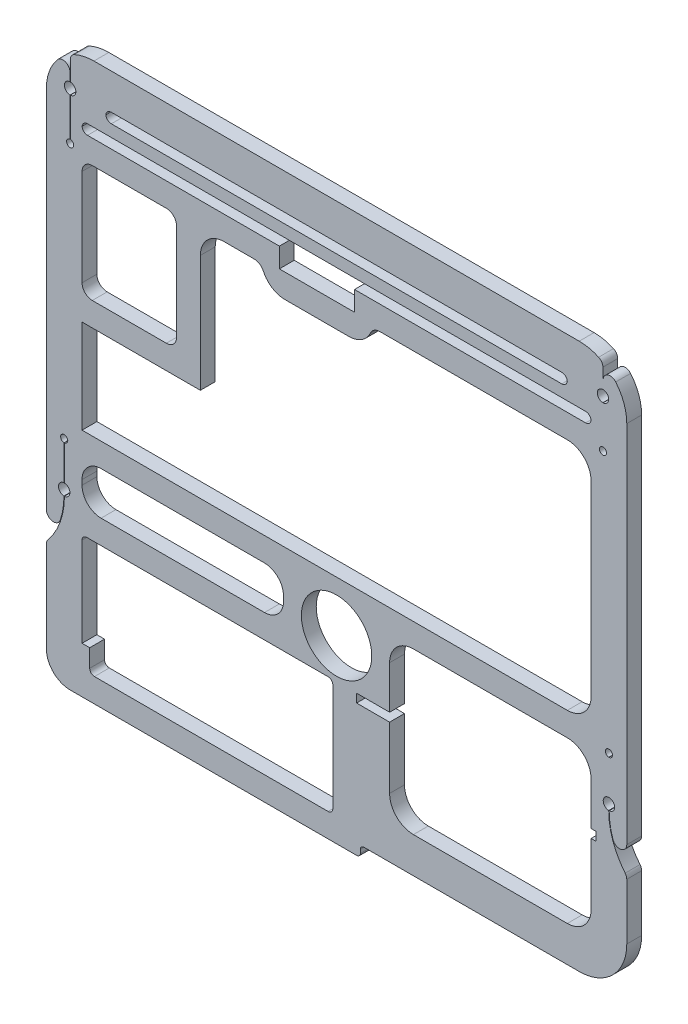
SolidWorks part; units mm, degrees
ref_plane "Front Plane" through (0, 0, 0) normal (0, 0, 1) x (1, 0, 0)
ref_plane "Top Plane" through (0, 0, 0) normal (0, 1, 0) x (1, 0, 0)
ref_plane "Right Plane" through (0, 0, 0) normal (1, 0, 0) x (0, 0, -1)
sketch "Sketch1" plane through (0, 0, 0) normal (0, 0, 1) x (1, 0, 0)
  line L0 (63.9883, 50.6392) -> (63.9883, 46.8292) construction
  line L1 (4.1102, -7.651) -> (66.0868, -7.651)
  line L2 (4.1102, -7.651) -> (4.1102, 50.6392)
  line L3 (4.1102, 50.6392) -> (66.0868, 50.6392)
  line L4 (66.0868, -7.651) -> (66.0868, 50.6392)
  line L5 (62.2768, 46.8292) -> (7.9202, 46.8292)
  line L6 (62.2768, 46.8292) -> (62.2768, -3.841)
  line L7 (62.2768, -3.841) -> (7.9202, -3.841)
  line L8 (7.9202, 46.8292) -> (7.9202, -3.841)
  line L9 (63.9883, 48.7342) -> (18.0707, 48.7342) construction
  line L10 (7.9202, 41.2855) -> (4.1102, 41.2855) construction
  line L11 (6.0152, 41.2855) -> (6.0152, 25.8577) construction
  line L12 (13.5248, -3.841) -> (13.5248, -7.651) construction
  line L13 (13.5248, -5.746) -> (21.1598, -5.746) construction
  line L14 (66.0868, 38.1916) -> (62.2768, 38.1916) construction
  line L15 (64.1818, 38.1916) -> (64.1818, 22.3321) construction
  line L16 (62.2768, 17.3639) -> (62.2768, 41.7492) construction
  line L17 (7.9202, 36.7962) -> (7.9202, 17.3639) construction
  line L22 (34.9556, 48.7342) -> (35.5018, 48.7342) construction
  line L23 (52.4244, -5.746) -> (51.8782, -5.746) construction
  dimension "D1" = 3.81
  dimension "D2" = 3.81
extrude "Boss-Extrude1" add sketch "Sketch1" along normal blind 1.5875
sketch "Sketch2" plane through (0, 0, 0) normal (0, 0, -1) x (-1, 0, 0)
  line L0 (-62.2768, -3.841) -> (-62.2768, 46.8292) construction
  line L1 (-62.2768, 15.868) -> (-7.9202, 15.868)
  line L2 (-62.2768, 15.868) -> (-62.2768, 13.328)
  line L3 (-62.2768, 13.328) -> (-7.9202, 13.328)
  line L4 (-7.9202, 15.868) -> (-7.9202, 13.328)
  line L5 (-7.9202, 46.8292) -> (-7.9202, -3.841) construction
  line L6 (-13.0532, 15.868) -> (-50.7532, 15.868) construction
  line L8 (-55.2788, 43.4256) -> (-16.9248, 43.4256) construction
  line L9 (-36.3812, 41.3174) -> (-29.6248, 41.3174) construction
  line L10 (-36.3812, 43.4256) -> (-36.3812, 41.3174) construction
  line L11 (-62.2768, 43.4256) -> (-37.0162, 43.4256)
  line L12 (-62.2768, 43.4256) -> (-62.2768, 40.8856)
  line L13 (-62.2768, 40.8856) -> (-38.9212, 40.8856)
  line L14 (-7.9202, 43.4256) -> (-7.9202, 40.8856)
  line L15 (-62.2768, 45.7624) -> (-7.9202, 45.7624)
  line L16 (-62.2768, 45.7624) -> (-62.2768, 44.4924)
  line L17 (-62.2768, 44.4924) -> (-7.9202, 44.4924)
  line L18 (-7.9202, 45.7624) -> (-7.9202, 44.4924)
  line L19 (-29.6248, 41.3174) -> (-29.6248, 43.4256) construction
  line L20 (-36.3812, 43.4256) -> (-36.3812, 41.3174) construction
  line L21 (-29.6248, 41.3174) -> (-29.6248, 43.4256) construction
  line L22 (-37.0162, 41.3174) -> (-37.0162, 43.4256)
  line L23 (-28.9898, 41.3174) -> (-37.0162, 41.3174)
  line L24 (-28.9898, 41.3174) -> (-28.9898, 43.4256)
  line L25 (-38.9212, 40.8856) -> (-38.9212, 38.7774)
  line L26 (-38.9212, 38.7774) -> (-27.0848, 38.7774)
  line L27 (-27.0848, 38.7774) -> (-27.0848, 40.8856)
  line L28 (-27.0848, 40.8856) -> (-7.9202, 40.8856)
  line L29 (-28.9898, 43.4256) -> (-7.9202, 43.4256)
  line L30 (-37.0162, 42.249) -> (-36.3812, 42.249) construction
  line L31 (-57.9086, 46.8292) -> (-57.9086, 45.7624) construction
  line L32 (-29.6248, 42.1673) -> (-28.9898, 42.1673) construction
  line L33 (-62.2768, 46.8292) -> (-7.9202, 46.8292) construction
  line L35 (-57.9086, 44.4924) -> (-57.9086, 43.4256) construction
  dimension "D1" = 2.54
  dimension "D2" = 1.905
  dimension "D3" = 2.54
  dimension "D4" = 1.905
  dimension "D5" = 1.27
  dimension "D6" = 0.635
extrude "Boss-Extrude2" add sketch "Sketch2" against normal up to surface (1.5875 mm away) up to face at (35.0985, 21.4941, 1.5875)
sketch "Sketch3" plane through (0, 0, 0) normal (0, 0, -1) x (-1, 0, 0)
  line L1 (-16.3032, 25.868) -> (-7.9202, 25.868) construction
  line L12 (-20.5532, 25.868) -> (-13.0532, 25.868)
  line L13 (-13.0532, 25.868) -> (-7.9202, 25.868)
  line L14 (-7.9202, 40.8856) -> (-7.9202, 15.868) construction
  line L15 (-7.9202, 25.868) -> (-7.9202, 28.408)
  line L16 (-7.9202, 28.408) -> (-18.0132, 28.408)
  line L17 (-18.0132, 28.408) -> (-18.0132, 40.8856)
  line L18 (-27.0848, 40.8856) -> (-7.9202, 40.8856) construction
  line L19 (-18.0132, 40.8856) -> (-20.5532, 40.8856)
  line L20 (-20.5532, 40.8856) -> (-20.5532, 25.868)
  line M27 (-27.0848, 40.8856) -> (-7.9202, 40.8856)
  line M28 (-7.9202, 40.8856) -> (-7.9202, 15.868)
  dimension "D3" = 2.54
  dimension "D4" = 2.54
extrude "Boss-Extrude3" add sketch "Sketch3" against normal up to surface (1.5875 mm away) contours L20 L12 L13 L16 L17 M27 M28 region at (20.3569, 33.3768, 0) up to face at (35.0985, 46.2958, 1.5875)
sketch "Sketch4" plane through (0, 0, 0) normal (0, 0, -1) x (-1, 0, 0)
  line L0 (-62.2768, 13.328) -> (-7.9202, 13.328) construction
  line L1 (-40.7627, 13.328) -> (-29.4343, 13.328)
  line L2 (-40.7627, 13.328) -> (-40.7627, -3.841)
  line L3 (-40.7627, -3.841) -> (-29.4343, -3.841)
  line L4 (-29.4343, 13.328) -> (-29.4343, -3.841)
  line L5 (-7.9202, -3.841) -> (-62.2768, -3.841) construction
  line L6 (-38.8577, 10.4578) -> (-40.7627, 10.4578) construction
  line L7 (-31.3393, 10.4578) -> (-29.4343, 10.4578) construction
  dimension "D1" = 1.905
extrude "Boss-Extrude4" add sketch "Sketch4" against normal up to surface (1.5875 mm away) up to face at (12.9667, 34.6468, 1.5875)
sketch "Sketch5" plane through (0, 0, 0) normal (0, 0, -1) x (-1, 0, 0)
  line L1 (-8.7364, -6.254) -> (-34.6952, -6.254) construction
  line L2 (-8.7364, -6.254) -> (-8.7364, 6.2047) construction
  line L6 (-8.7364, 6.2047) -> (-34.6952, 6.2047) construction
  line L7 (-34.6952, -6.254) -> (-34.6952, 6.2047) construction
  line L8 (-8.7364, -6.254) -> (-34.6952, -6.254)
  line L9 (-8.7364, -6.254) -> (-8.7364, 6.2047)
  line L10 (-8.7364, 6.2047) -> (-34.6952, 6.2047)
  line L11 (-34.6952, -6.254) -> (-34.6952, 6.2047)
  circle A1 centre (-35.0985, 10.4578) radius 3.7592 construction
  circle A2 centre (-35.0985, 10.4578) radius 3.7592
extrude "Cut-Extrude1" cut sketch "Sketch5" against normal up to surface (1.5875 mm away) up to face at (51.5197, 4.7435, 1.5875)
sketch "Sketch10" plane through (0, 0, 1.5875) normal (0, 0, 1) x (1, 0, 0)
  line L0 (29.4343, 13.328) -> (29.4343, 6.2047) construction
  line L1 (7.9202, 6.2047) -> (29.4343, 6.2047)
  line L2 (7.9202, 6.2047) -> (7.9202, 8.7447)
  line L3 (7.9202, 8.7447) -> (29.4343, 8.7447)
  line L4 (29.4343, 6.2047) -> (29.4343, 8.7447)
  line L5 (7.9202, 13.328) -> (7.9202, -3.841) construction
  line L6 (34.6952, 6.2047) -> (29.4343, 6.2047) construction
  dimension "D1" = 2.54
extrude "Boss-Extrude5" add sketch "Sketch10" against normal up to surface (1.5875 mm away) up to face at (20.1965, 2.3595, 0)
fillet "Fillet1" radius 5.08 3 edges at (66.0868, -7.651, 0.7937) (4.1102, 50.6392, 0.7937) (66.0868, 50.6392, 0.7937)
fillet "Fillet2" radius 2.54 5 edges at (20.5532, 40.8856, 0.7937) (27.0848, 38.7774, 0.7937) (62.2768, 40.8856, 0.7937) (62.2768, 15.868, 0.7937) (38.9212, 38.7774, 0.7937)
fillet "Fillet3" radius 1.0922 6 edges at (7.9202, 28.408, 0.7937) (18.0132, 28.408, 0.7937) (7.9202, 40.8856, 0.7937) (18.0132, 40.8856, 0.7937) (27.0848, 40.8856, 0.7937) (38.9212, 40.8856, 0.7937)
fillet "Fillet4" radius 0.5842 4 edges at (7.9202, 43.4256, 0.7937) (7.9202, 44.4924, 0.7937) (62.2768, 44.4924, 0.7937) (62.2768, 43.4256, 0.7937)
sketch "Sketch6" plane through (0, 0, 0) normal (0, 0, -1) x (-1, 0, 0)
  line L0 (-9.5532, 24.368) -> (-9.5532, 17.368) construction
  line L1 (-9.5532, 24.368) -> (-9.5532, 17.368)
  line L2 (-11.0532, 25.868) -> (-9.5532, 24.368) construction
  line L3 (-11.0532, 25.868) -> (-9.5532, 24.368)
  line L4 (-11.0532, 25.868) -> (-11.0532, 15.868)
  line L6 (-13.0532, 17.368) -> (-13.0532, 15.868)
  line L7 (-13.0532, 15.868) -> (-11.0532, 15.868)
  line L8 (-11.0532, 15.868) -> (-9.5532, 17.368)
  line L9 (-9.5532, 17.368) -> (-13.0532, 17.368)
  line L12 (-11.0532, 15.868) -> (-9.5532, 17.368)
  circle A0 centre (-63.5468, 46.8292) radius 0.6096 construction
  circle A1 centre (-6.6502, 46.8292) radius 0.6096 construction
  circle A2 centre (-64.1818, 9.4264) radius 0.6096 construction
  circle A3 centre (-6.0152, 9.4264) radius 0.6096 construction
  circle A4 centre (-63.5468, 46.8292) radius 0.6096
  circle A5 centre (-6.6502, 46.8292) radius 0.6096
  circle A6 centre (-64.1818, 9.4264) radius 0.6096
  circle A7 centre (-6.0152, 9.4264) radius 0.6096
  dimension "D1" = 0
extrude "Cut-Extrude2" cut sketch "Sketch6" against normal up to surface (1.5875 mm away) up to face at (17.1172, -1.2967, 1.5875)
sketch "Sketch9" plane through (0, 0, 1.5875) normal (0, 0, 1) x (1, 0, 0)
  line L4 (62.813, 6.2047) -> (37.2352, 6.2047)
  line L5 (37.2352, 6.2047) -> (37.2352, 5.2903)
  line L6 (37.2352, 5.2903) -> (62.813, 5.2903)
  line L7 (62.813, 5.2903) -> (62.813, 6.2047)
  line L8 (62.813, 6.2047) -> (37.2352, 6.2047)
  line L9 (37.2352, 6.2047) -> (37.2352, 5.2903)
  line L10 (37.2352, 5.2903) -> (62.813, 5.2903)
  line L11 (62.813, 5.2903) -> (62.813, 6.2047)
  dimension "D1" = 0
extrude "Cut-Extrude3" cut sketch "Sketch9" against normal up to surface (1.5875 mm away) up to face at (5.4056, 9.4264, 0)
fillet "Fillet6" radius 0.508 4 edges at (34.6952, 6.2047, 0.7937) (34.6952, -6.254, 0.7937) (8.7364, -6.254, 0.7937) (7.9202, 6.2047, 0.7937)
sketch "Sketch11" plane through (0, 0, 1.5875) normal (0, 0, 1) x (1, 0, 0)
  line L0 (9.2444, -6.254) -> (34.1872, -6.254) construction
  line L1 (4.1102, -7.651) -> (37.6385, -7.651)
  line L2 (4.1102, -7.651) -> (4.1102, -8.794)
  line L3 (4.1102, -8.794) -> (37.6385, -8.794)
  line L4 (37.6385, -7.651) -> (37.6385, -8.794)
  line L5 (35.0985, 14.217) -> (35.0985, -22.2214) construction
  circle A0 centre (35.0985, 10.4578) radius 3.7592 construction
  dimension "D1" = 2.54
  dimension "D2" = 2.54
extrude "Boss-Extrude6" add sketch "Sketch11" against normal up to surface (1.5875 mm away) up to face at (51.0212, 5.4129, 0)
fillet "Fillet7" radius 2.54 1 edges at (4.1102, -8.794, 0.7937)
fillet "Fillet8" radius 0.381 2 edges at (37.6385, -8.794, 0.7937) (37.6385, -7.651, 0.7937)
fillet "Fillet9" radius 2.032 4 edges at (29.4343, 8.7447, 0.7937) (29.4343, 13.328, 0.7937) (7.9202, 8.7447, 0.7937) (7.9202, 13.328, 0.7937)
fillet "Fillet10" radius 2.54 4 edges at (40.7627, -3.841, 0.7937) (62.2768, -3.841, 0.7937) (62.2768, 13.328, 0.7937) (40.7627, 13.328, 0.7937)
sketch "Sketch12" plane through (0, 0, 1.5875) normal (0, 0, 1) x (1, 0, 0)
  line L0 (7.9202, 46.8292) -> (7.9202, 45.7624) construction
  line L1 (7.9202, 46.8292) -> (10.4602, 46.8292)
  line L2 (7.9202, 46.8292) -> (7.9202, 45.7624)
  line L3 (7.9202, 45.7624) -> (10.4602, 45.7624)
  line L4 (10.4602, 46.8292) -> (10.4602, 45.7624)
  line L5 (62.2768, 46.8292) -> (7.9202, 46.8292) construction
  line L6 (62.2768, 45.7624) -> (7.9202, 45.7624) construction
  line L8 (62.2768, 46.8292) -> (59.7368, 46.8292)
  line L9 (62.2768, 46.8292) -> (62.2768, 45.7624)
  line L10 (62.2768, 45.7624) -> (59.7368, 45.7624)
  line L11 (59.7368, 46.8292) -> (59.7368, 45.7624)
  dimension "D1" = 2.54
extrude "Boss-Extrude7" add sketch "Sketch12" against normal up to surface (1.5875 mm away) up to face at (51.1458, 5.2455, 0)
fillet "Fillet11" radius 0.5842 4 edges at (59.7368, 45.7624, 0.7937) (59.7368, 46.8292, 0.7937) (10.4602, 45.7624, 0.7937) (10.4602, 46.8292, 0.7937)
sketch "Sketch13" plane through (0, 0, 1.5875) normal (0, 0, 1) x (1, 0, 0)
  line L0 (6.6375, 48.3265) -> (6.6375, 47.4387) construction
  line L1 (6.6629, 47.4387) -> (6.6629, 49.4999) construction
  line L2 (6.6375, 46.2198) -> (6.6375, 42.13) construction
  line L3 (6.6629, 42.13) -> (6.6629, 46.2198) construction
  line L4 (63.5341, 47.4387) -> (63.5341, 49.4999) construction
  line L5 (63.5595, 46.2198) -> (63.5595, 42.13) construction
  line L6 (63.5341, 42.13) -> (63.5341, 46.2198) construction
  line L7 (64.1945, 13.745) -> (64.1945, 10.0359) construction
  line L8 (64.1691, 13.745) -> (64.1691, 10.0359) construction
  line L9 (6.0025, 13.745) -> (6.0025, 10.0359) construction
  line L10 (6.0279, 13.745) -> (6.0279, 10.0359) construction
  line L11 (6.6375, 48.3265) -> (6.6375, 47.4387)
  line L12 (6.6629, 47.4387) -> (6.6629, 49.4999)
  line L13 (6.6375, 46.2198) -> (6.6375, 42.13)
  line L14 (6.6629, 42.13) -> (6.6629, 46.2198)
  line L15 (63.5341, 47.4387) -> (63.5341, 49.4999)
  line L16 (63.5595, 46.2198) -> (63.5595, 42.13)
  line L17 (63.5341, 42.13) -> (63.5341, 46.2198)
  line L18 (64.1945, 13.745) -> (64.1945, 10.0359)
  line L19 (64.1691, 13.745) -> (64.1691, 10.0359)
  line L20 (6.0025, 13.745) -> (6.0025, 10.0359)
  line L21 (6.0279, 13.745) -> (6.0279, 10.0359)
  line L22 (4.1102, 45.5592) -> (4.1102, -6.254) construction
  line L23 (66.0868, -2.571) -> (66.0868, 45.5592) construction
  line L24 (4.1102, 6.6241) -> (4.1102, 3.4186)
  line L25 (66.0868, 3.4186) -> (66.0868, 6.6241)
  line L26 (63.5595, 46.2198) -> (63.5595, 42.13)
  line L27 (63.5595, 48.3265) -> (63.5595, 47.4387) construction
  line L28 (63.5595, 48.3265) -> (63.5595, 47.4387)
  arc A0 (63.5341, 46.2198) -> (63.5595, 46.2198) centre (63.5468, 46.8292) ccw
  arc A1 (6.6375, 48.3265) -> (5.2905, 48.8149) centre (5.8755, 48.3265) ccw construction
  arc A2 (7.1133, 50.1953) -> (6.6629, 49.4999) centre (7.4249, 49.4999) ccw construction
  arc A3 (6.6375, 42.13) -> (6.6629, 42.13) centre (6.6502, 41.7492) ccw construction
  arc A4 (63.5341, 49.4999) -> (63.0836, 50.1953) centre (62.7721, 49.4999) ccw construction
  arc A5 (64.9064, 48.8149) -> (63.5595, 48.3265) centre (64.3215, 48.3265) ccw construction
  arc A6 (63.5341, 42.13) -> (63.5595, 42.13) centre (63.5468, 41.7492) ccw construction
  arc A7 (64.1945, 13.745) -> (64.1691, 13.745) centre (64.1818, 14.1258) ccw construction
  arc A8 (64.2072, 8.8174) -> (64.6018, 6.3833) centre (71.9076, 8.8168) ccw construction
  arc A9 (64.6018, 6.3833) -> (66.0868, 6.6241) centre (65.3248, 6.6241) ccw construction
  arc A10 (64.1564, 8.8174) -> (65.914, 3.9017) centre (71.9076, 8.8168) ccw construction
  arc A11 (66.0868, 3.4186) -> (65.914, 3.9017) centre (65.3248, 3.4186) ccw construction
  arc A12 (4.1102, 6.6241) -> (5.5951, 6.3833) centre (4.8722, 6.6241) ccw construction
  arc A13 (6.0279, 13.745) -> (6.0025, 13.745) centre (6.0152, 14.1258) ccw construction
  arc A14 (4.2829, 3.9017) -> (6.0406, 8.8174) centre (-1.7107, 8.8168) ccw construction
  arc A15 (5.5951, 6.3833) -> (5.9898, 8.8174) centre (-1.7107, 8.8168) ccw construction
  arc A16 (4.2829, 3.9017) -> (4.1102, 3.4186) centre (4.8722, 3.4186) ccw construction
  arc A17 (6.6375, 46.2198) -> (6.6629, 46.2198) centre (6.6502, 46.8292) ccw
  arc A18 (6.6375, 48.3265) -> (5.2905, 48.8149) centre (5.8755, 48.3265) ccw
  arc A19 (7.1133, 50.1953) -> (6.6629, 49.4999) centre (7.4249, 49.4999) ccw
  arc A20 (6.6375, 42.13) -> (6.6629, 42.13) centre (6.6502, 41.7492) ccw
  arc A21 (63.5341, 49.4999) -> (63.0836, 50.1953) centre (62.7721, 49.4999) ccw
  arc A22 (64.9064, 48.8149) -> (63.5595, 48.3265) centre (64.3215, 48.3265) ccw
  arc A23 (63.5341, 42.13) -> (63.5595, 42.13) centre (63.5468, 41.7492) ccw
  arc A24 (64.1945, 13.745) -> (64.1691, 13.745) centre (64.1818, 14.1258) ccw
  arc A25 (64.2072, 8.8174) -> (64.6018, 6.3833) centre (71.9076, 8.8168) ccw
  arc A26 (64.6018, 6.3833) -> (66.0868, 6.6241) centre (65.3248, 6.6241) ccw
  arc A27 (64.1564, 8.8174) -> (65.914, 3.9017) centre (71.9076, 8.8168) ccw
  arc A28 (66.0868, 3.4186) -> (65.914, 3.9017) centre (65.3248, 3.4186) ccw
  arc A29 (4.1102, 6.6241) -> (5.5951, 6.3833) centre (4.8722, 6.6241) ccw
  arc A30 (6.0279, 13.745) -> (6.0025, 13.745) centre (6.0152, 14.1258) ccw
  arc A31 (4.2829, 3.9017) -> (6.0406, 8.8174) centre (-1.7107, 8.8168) ccw
  arc A32 (5.5951, 6.3833) -> (5.9898, 8.8174) centre (-1.7107, 8.8168) ccw
  arc A33 (4.2829, 3.9017) -> (4.1102, 3.4186) centre (4.8722, 3.4186) ccw
  circle A34 centre (6.6502, 46.8292) radius 0.6096 construction
  circle A35 centre (63.5468, 46.8292) radius 0.6096 construction
  circle A36 centre (64.1818, 9.4264) radius 0.6096 construction
  circle A37 centre (6.0152, 9.4264) radius 0.6096 construction
  arc A38 (9.1902, 50.6392) -> (4.1102, 45.5592) centre (9.1902, 45.5592) ccw construction
  arc A39 (66.0868, 45.5592) -> (61.0068, 50.6392) centre (61.0068, 45.5592) ccw construction
  arc A40 (6.6629, 47.4387) -> (6.6375, 47.4387) centre (6.6502, 46.8292) ccw
  arc A41 (63.5341, 46.2198) -> (63.5595, 46.2198) centre (63.5468, 46.8292) ccw
  arc A42 (64.1945, 10.0359) -> (64.1691, 10.0359) centre (64.1818, 9.4264) ccw
  arc A43 (5.9898, 8.8174) -> (6.0406, 8.8174) centre (6.0152, 9.4264) ccw
  arc A44 (7.1133, 50.1953) -> (5.2905, 48.8149) centre (9.1902, 45.5592) ccw
  arc A45 (64.9064, 48.8149) -> (63.0836, 50.1953) centre (61.0068, 45.5592) ccw
  arc A46 (6.0279, 10.0359) -> (6.0025, 10.0359) centre (6.0152, 9.4264) ccw
  arc A47 (64.1564, 8.8174) -> (64.2072, 8.8174) centre (64.1818, 9.4264) ccw
  arc A48 (63.5595, 47.4387) -> (63.5341, 47.4387) centre (63.5468, 46.8292) ccw
extrude "Cut-Extrude4" cut sketch "Sketch13" against normal through all contours A48 L28 A22 A45 A21 L15 | L17 A23 L16 A0 | A47 A27 A28 L25 A26 A25 | A42 L18 A24 L19 | A43 A32 A29 L24 A33 A31 | A46 L21 A30 L20 | A19 A44 A18 L11 A40 L12 | L13 A20 L14 A17 region at (6.3322, 49.2741, 1.5875) region at (6.6502, 42.1993, 1.5875) region at (63.8647, 49.2741, 1.5875) region at (63.5468, 42.1993, 1.5875) region at (64.1818, 13.7431, 1.5875) region at (6.0152, 13.7431, 1.5875) region at (4.6816, 5.348, 1.5875) region at (65.5153, 5.348, 1.5875)
